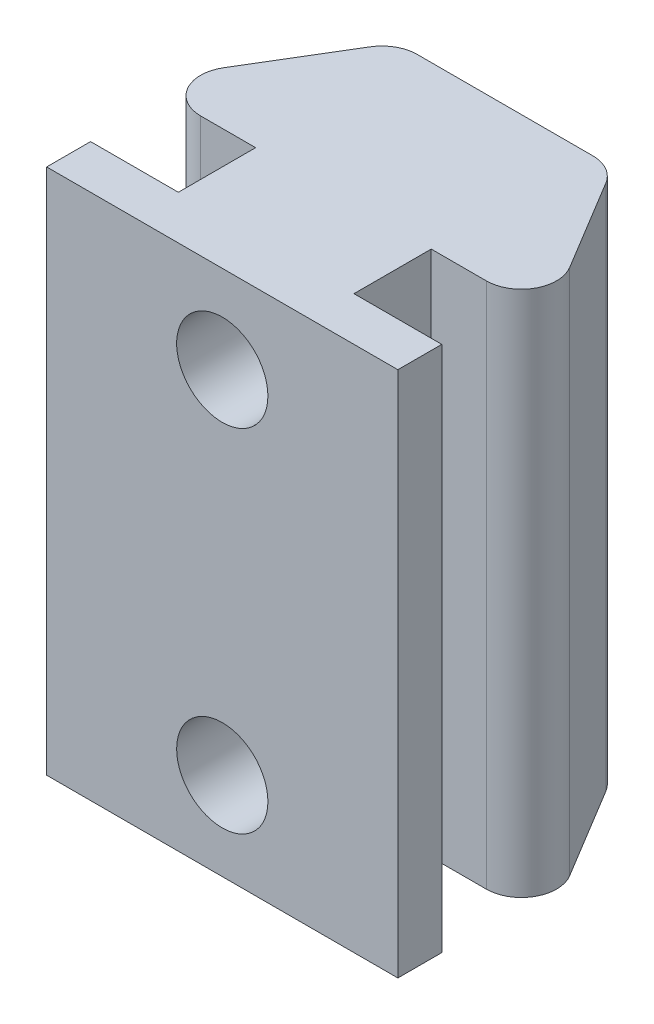
SolidWorks part; units mm, degrees
ref_plane "Front Plane" through (0, 0, 0) normal (0, 0, 1) x (1, 0, 0)
ref_plane "Top Plane" through (0, 0, 0) normal (0, 1, 0) x (1, 0, 0)
ref_plane "Right Plane" through (0, 0, 0) normal (1, 0, 0) x (0, 0, -1)
sketch "Sketch1" plane through (0, 0, 0) normal (0, 0, 1) x (1, 0, 0)
  line L0 (-6.35, 0) -> (6.35, 0) construction
  line L1 (-6.35, -9.525) -> (6.35, -9.525)
  line L2 (-6.35, -9.525) -> (-6.35, 9.525)
  line L3 (-6.35, 9.525) -> (6.35, 9.525)
  line L4 (6.35, -9.525) -> (6.35, 9.525)
  line L5 (-6.35, -9.525) -> (6.35, 9.525) construction
  line L6 (-6.35, 9.525) -> (6.35, -9.525) construction
  line L8 (-6.35, 9.525) -> (0, 9.525)
  point P0 (0, 0)
  point P9 (0, 0)
  point P16 (2.0493, 8.6644)
  dimension "D1" = 19.05
  dimension "D2" = 12.7
extrude "Boss-Extrude1" add sketch "Sketch1" along normal blind 1.5875 contours L2 L1 L4 L3
sketch "Sketch2" plane through (0, 9.525, 0) normal (0, 1, 0) x (1, 0, 0)
  line L0 (0, 0) -> (0, 8.636) construction
  line L1 (3.175, 0) -> (3.175, 2.794)
  line L2 (-6.35, 0) -> (6.35, 0) construction
  line L3 (3.175, 2.794) -> (5.1673, 2.794)
  line L4 (6.2547, 4.7201) -> (4.2624, 8.0221)
  line L5 (3.175, 8.636) -> (-3.175, 8.636)
  line L6 (3.175, 0) -> (-3.175, 0)
  line L7 (-3.175, 0) -> (-3.175, 2.794)
  line L8 (-3.175, 2.794) -> (-5.1673, 2.794)
  line L9 (-6.2547, 4.7201) -> (-4.2624, 8.0221)
  arc A0 (4.2624, 8.0221) -> (3.175, 8.636) centre (3.175, 7.366) ccw
  arc A1 (5.1673, 2.794) -> (6.2547, 4.7201) centre (5.1673, 4.064) ccw
  arc A2 (-5.1673, 2.794) -> (-6.2547, 4.7201) centre (-5.1673, 4.064) cw
  arc A3 (-4.2624, 8.0221) -> (-3.175, 8.636) centre (-3.175, 7.366) cw
  point P7 (4.3474, 2.3622)
  point P10 (0, 0)
  point P11 (0, 0)
  point P16 (2.9224, 8.2042)
  point P19 (3.892, 8.636)
  point P22 (7.4168, 2.794)
  point P25 (-7.4168, 2.794)
  point P28 (-3.892, 8.636)
  dimension "D5" = 1.27
  dimension "D1" = 8.636
  dimension "D2" = 6.35
  dimension "D3" = 5.842
  dimension "D4" = 14.8336
extrude "Boss-Extrude2" add sketch "Sketch2" against normal up to surface (19.05 mm away) up to face at (0, -9.525, 0.7937)
sketch "Sketch4" plane through (0, 0, 1.5875) normal (0, 0, 1) x (1, 0, 0)
  line L0 (-6.35, 0) -> (6.35, 0) construction
  line L1 (-6.35, -9.525) -> (-6.35, 9.525) construction
  line L2 (6.35, -9.525) -> (6.35, 9.525) construction
  line L3 (-6.35, 9.525) -> (6.35, 9.525) construction
  circle A0 centre (0, 6.35) radius 1.65
  circle A1 centre (0, -6.35) radius 1.65
  point P8 (0, 0)
  point P10 (0, 7.3255)
  dimension "D1" = 3.3
  dimension "D2" = 3.175
extrude "Cut-Extrude1" cut sketch "Sketch4" against normal up to surface (4.3815 mm away) up to face at (4.1711, 0, -2.794)
